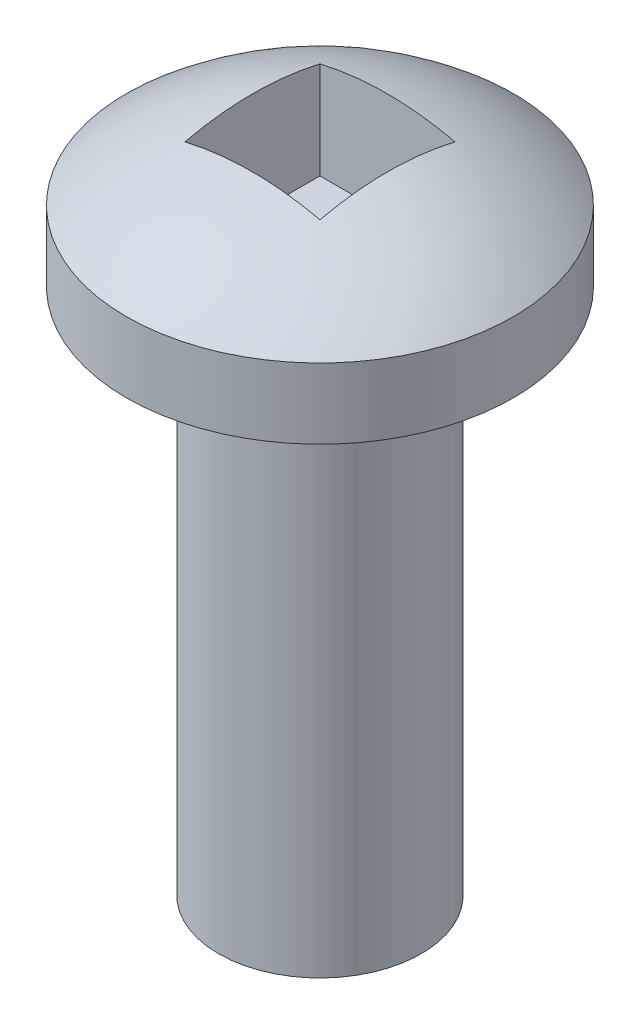
SolidWorks part; units mm, degrees
material "Cast Alloy Steel"
ref_plane "Front Plane" through (0, 0, 0) normal (0, 0, 1) x (1, 0, 0)
ref_plane "Top Plane" through (0, 0, 0) normal (0, 1, 0) x (1, 0, 0)
ref_plane "Right Plane" through (0, 0, 0) normal (1, 0, 0) x (0, 0, -1)
sketch "Sketch1" plane through (0, 0, 0) normal (0, 1, 0) x (1, 0, 0)
  circle A0 centre (0, 0) radius 1.8288
  dimension "D1" = 3.6576
extrude "Boss-Extrude1" add sketch "Sketch1" against normal blind 9.525
sketch "Sketch2" plane through (0, 0, 0) normal (0, 1, 0) x (1, 0, 0)
  circle A0 centre (0, 0) radius 3.4925
  dimension "D1" = 6.985
extrude "Boss-Extrude2" add sketch "Sketch2" along normal blind 1.27
dome "Dome1" faces to dome 1 distance 1.27 reverse direction no elliptical dome no face at (0, 1.27, 3.4925) parameters "D1"=1.27
ref_plane "Plane1" through (0, 2.54, 0) normal (0, 1, 0) x (1, 0, 0)
sketch "Sketch3" plane through (0, 2.54, 0) normal (0, 1, 0) x (1, 0, 0)
  line L1 (-1.2192, -1.2192) -> (1.2192, -1.2192)
  line L2 (-1.2192, -1.2192) -> (-1.2192, 1.2192)
  line L3 (-1.2192, 1.2192) -> (1.2192, 1.2192)
  line L4 (1.2192, -1.2192) -> (1.2192, 1.2192)
  line L5 (-1.2192, -1.2192) -> (1.2192, 1.2192) construction
  line L6 (-1.2192, 1.2192) -> (1.2192, -1.2192) construction
  point P0 (0, 0)
  dimension "D1" = 2.4384
extrude "Cut-Extrude1" cut sketch "Sketch3" against normal blind 2.032
